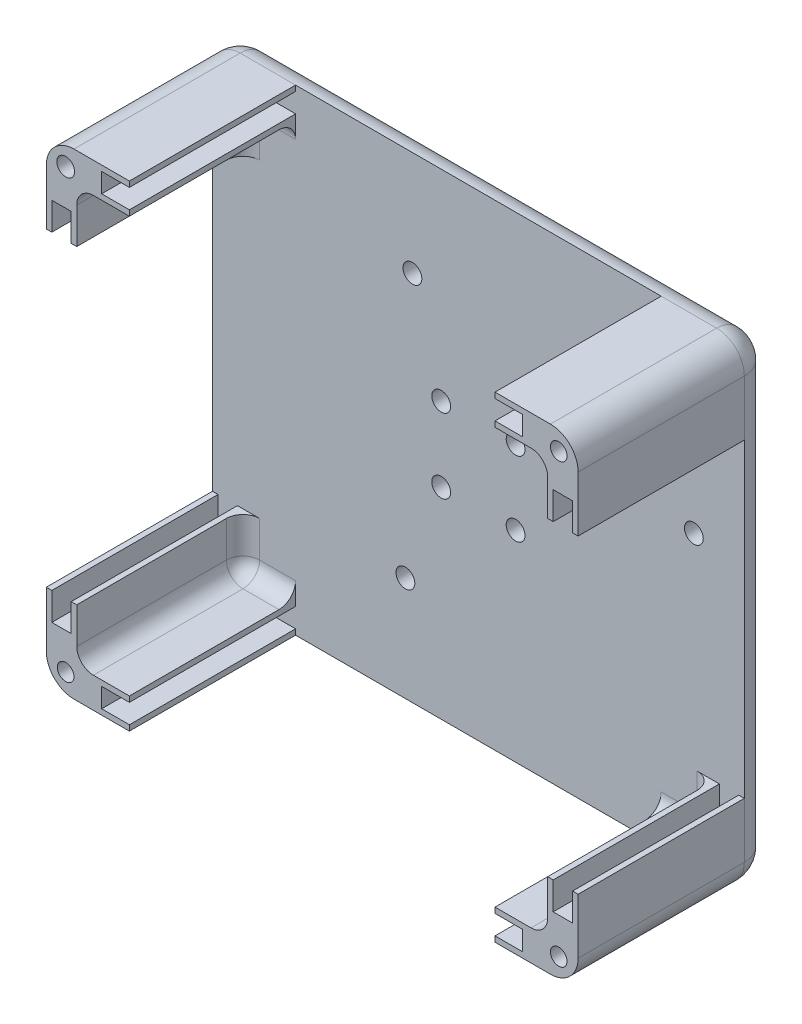
SolidWorks part; units mm, degrees
ref_plane "Plan de face" through (0, 0, 0) normal (0, 0, 1) x (1, 0, 0)
ref_plane "Plan de dessus" through (0, 0, 0) normal (0, 1, 0) x (1, 0, 0)
ref_plane "Plan de droite" through (0, 0, 0) normal (1, 0, 0) x (0, 0, -1)
sketch "Esquisse1" plane through (0, 0, 0) normal (0, 0, 1) x (1, 0, 0)
  line L1 (50.2, -56.1595) -> (-45.8, -56.1595)
  line L2 (50.2, -56.1595) -> (50.2, 29.8405)
  line L3 (50.2, 29.8405) -> (-45.8, 29.8405)
  line L4 (-45.8, -56.1595) -> (-45.8, 29.8405)
  point P0 (0, 0)
  dimension "D1" = 96
  dimension "D2" = 86
extrude "Boss.-Extru.1" add sketch "Esquisse1" along normal blind 5
sketch "trou_support_moteur" plane through (0, 0, 5) normal (0, 0, 1) x (1, 0, 0)
  circle A0 centre (2.2, -13.1595) radius 9.5 construction
  dimension "D1" = 19
sketch "Esquisse33" plane through (0, 0, 5) normal (0, 0, 1) x (1, 0, 0)
  line L1 (-4.5175, -6.4419) -> (8.9175, -6.4419) construction
  line L2 (-4.5175, -6.4419) -> (-4.5175, -19.877) construction
  line L3 (-4.5175, -19.877) -> (8.9175, -19.877) construction
  line L4 (8.9175, -6.4419) -> (8.9175, -19.877) construction
  line L5 (-4.5175, -6.4419) -> (8.9175, -19.877) construction
  line L6 (-4.5175, -19.877) -> (8.9175, -6.4419) construction
  circle A0 centre (2.2, -13.1595) radius 9.5 construction
  point P0 (2.2, -13.1595)
sketch "Esquisse2" plane through (0, 0, 5) normal (0, 0, 1) x (1, 0, 0)
  line L16 (-45.8, 29.8405) -> (-45.8, 14.8405)
  line L17 (-45.8, 29.8405) -> (-45.8, -56.1595) construction
  line L18 (-45.8, 14.8405) -> (-44.8, 14.8405)
  line L19 (-44.8, 14.8405) -> (-44.8, 19.8405)
  line L20 (-44.8, 19.8405) -> (-41.3, 19.8405)
  line L21 (-41.3, 19.8405) -> (-41.3, 14.8405)
  line L22 (-41.3, 14.8405) -> (-40.3, 14.8405)
  line L23 (-40.3, 14.8405) -> (-40.3, 24.3405)
  line L24 (-40.3, 24.3405) -> (-30.8, 24.3405)
  line L25 (-30.8, 24.3405) -> (-30.8, 25.3405)
  line L26 (-30.8, 25.3405) -> (-35.8, 25.3405)
  line L27 (-35.8, 25.3405) -> (-35.8, 28.8405)
  line L28 (-35.8, 28.8405) -> (-30.8, 28.8405)
  line L29 (-30.8, 28.8405) -> (-30.8, 29.8405)
  line L30 (50.2, 29.8405) -> (-45.8, 29.8405) construction
  line L31 (-30.8, 29.8405) -> (-45.8, 29.8405)
  dimension "D2" = 5
  dimension "D3" = 5
  dimension "D4" = 5
  dimension "D5" = 5
  dimension "D6" = 3.5
  dimension "D7" = 3.5
  dimension "D8" = 1
  dimension "D9" = 1
  dimension "D10" = 15
  dimension "D11" = 1
  dimension "D12" = 1
  dimension "D13" = 15
extrude "Boss.-Extru.4" add sketch "Esquisse2" along normal blind 30
fillet "Congé2" radius 5 4 edges at (-45.8, -13.1595, 0) (2.2, -56.1595, 0) (50.2, -13.1595, 0) (2.2, 29.8405, 0)
sketch "Esquisse4" plane through (0, 0, 35) normal (0, 0, 1) x (1, 0, 0)
  line L0 (-45.8, 29.8405) -> (-45.8, 14.8405) construction
  line L1 (-30.8, 29.8405) -> (-45.8, 29.8405) construction
  circle A0 centre (-42.3, 26.3405) radius 1.6
  dimension "D1" = 3.2
  dimension "D2" = 3.5
  dimension "D3" = 3.5
extrude "Enlèv. mat.-Extru.1" cut sketch "Esquisse4" against normal blind 10
sketch "Esquisse14" plane through (0, 0, 5) normal (0, 0, 1) x (1, 0, 0)
  line L0 (-45.8, -56.1595) -> (-45.8, -41.1595)
  line L1 (-45.8, 14.8405) -> (-45.8, -56.1595) construction
  line L2 (-45.8, -41.1595) -> (-44.8, -41.1595)
  line L3 (-44.8, -41.1595) -> (-44.8, -46.1595)
  line L4 (-44.8, -46.1595) -> (-41.3, -46.1595)
  line L5 (-41.3, -46.1595) -> (-41.3, -41.1595)
  line L6 (-41.3, -41.1595) -> (-40.3, -41.1595)
  line L7 (-40.3, -41.1595) -> (-40.3, -50.6595)
  line L8 (-40.3, -50.6595) -> (-30.8, -50.6595)
  line L9 (-30.8, -50.6595) -> (-30.8, -51.6595)
  line L10 (-30.8, -51.6595) -> (-35.8, -51.6595)
  line L11 (-35.8, -51.6595) -> (-35.8, -55.1595)
  line L12 (-35.8, -55.1595) -> (-30.8, -55.1595)
  line L13 (-30.8, -55.1595) -> (-30.8, -56.1595)
  line L14 (-45.8, -56.1595) -> (50.2, -56.1595) construction
  line L15 (-30.8, -56.1595) -> (-45.8, -56.1595)
  dimension "D1" = 15
  dimension "D2" = 15
  dimension "D3" = 5
  dimension "D4" = 5
  dimension "D5" = 3.5
  dimension "D6" = 1
  dimension "D7" = 1
  dimension "D8" = 5
  dimension "D9" = 5
  dimension "D10" = 1
  dimension "D11" = 1
  dimension "D12" = 3.5
sketch "Esquisse21" plane through (0, 0, 5) normal (0, 0, 1) x (1, 0, 0)
  line L0 (-45.8, -56.1595) -> (-45.8, -41.1595)
  line L1 (-45.8, 14.8405) -> (-45.8, -56.1595) construction
  line L2 (-45.8, -41.1595) -> (-44.8, -41.1595)
  line L3 (-44.8, -41.1595) -> (-44.8, -46.1595)
  line L4 (-44.8, -46.1595) -> (-41.3, -46.1595)
  line L5 (-41.3, -46.1595) -> (-41.3, -41.1595)
  line L6 (-41.3, -41.1595) -> (-40.3, -41.1595)
  line L7 (-40.3, -41.1595) -> (-40.3, -50.6595)
  line L8 (-40.3, -50.6595) -> (-30.8, -50.6595)
  line L9 (-30.8, -50.6595) -> (-30.8, -51.6595)
  line L10 (-30.8, -51.6595) -> (-35.8, -51.6595)
  line L11 (-35.8, -51.6595) -> (-35.8, -55.1595)
  line L12 (-35.8, -55.1595) -> (-30.8, -55.1595)
  line L13 (-30.8, -55.1595) -> (-30.8, -56.1595)
  line L14 (-45.8, -56.1595) -> (50.2, -56.1595) construction
  line L15 (-30.8, -56.1595) -> (-45.8, -56.1595)
  dimension "D1" = 15
  dimension "D2" = 15
  dimension "D3" = 5
  dimension "D4" = 5
  dimension "D5" = 5
  dimension "D6" = 5
  dimension "D7" = 1
  dimension "D8" = 1
  dimension "D9" = 3.5
  dimension "D10" = 1
  dimension "D11" = 1
  dimension "D12" = 3.5
extrude "Boss.-Extru.17" add sketch "Esquisse21" along normal blind 30
sketch "Esquisse22" plane through (0, 0, 35) normal (0, 0, 1) x (1, 0, 0)
  line L0 (-45.8, -56.1595) -> (-30.8, -56.1595) construction
  line L1 (-45.8, -41.1595) -> (-45.8, -56.1595) construction
  circle A0 centre (-42.3, -52.6595) radius 1.5
  dimension "D1" = 3
  dimension "D2" = 3.5
  dimension "D3" = 3.5
extrude "Enlèv. mat.-Extru.5" cut sketch "Esquisse22" against normal blind 10
extrude "Boss.-Extru.14" add sketch "Esquisse14" along normal blind 20
sketch "Esquisse16" plane through (0, 0, 5) normal (0, 0, 1) x (1, 0, 0)
  line L0 (50.2, 29.8405) -> (35.2, 29.8405)
  line L1 (50.2, 29.8405) -> (-30.8, 29.8405) construction
  line L2 (35.2, 29.8405) -> (35.2, 28.8405)
  line L3 (35.2, 28.8405) -> (40.2, 28.8405)
  line L4 (40.2, 28.8405) -> (40.2, 25.3405)
  line L5 (40.2, 25.3405) -> (35.2, 25.3405)
  line L6 (35.2, 25.3405) -> (35.2, 24.3405)
  line L7 (35.2, 24.3405) -> (44.7, 24.3405)
  line L8 (44.7, 24.3405) -> (44.7, 14.8405)
  line L9 (44.7, 14.8405) -> (45.7, 14.8405)
  line L10 (45.7, 14.8405) -> (45.7, 19.8405)
  line L11 (45.7, 19.8405) -> (49.2, 19.8405)
  line L12 (49.2, 19.8405) -> (49.2, 14.8405)
  line L13 (49.2, 14.8405) -> (50.2, 14.8405)
  line L14 (50.2, -56.1595) -> (50.2, 29.8405) construction
  line L15 (50.2, 14.8405) -> (50.2, 29.8405)
  dimension "D1" = 15
  dimension "D2" = 15
  dimension "D3" = 5
  dimension "D4" = 5
  dimension "D5" = 5
  dimension "D6" = 5
  dimension "D7" = 1
  dimension "D8" = 1
  dimension "D9" = 3.5
  dimension "D10" = 1
  dimension "D11" = 1
  dimension "D12" = 3.5
extrude "Boss.-Extru.15" add sketch "Esquisse16" along normal blind 30
sketch "Esquisse17" plane through (0, 0, 35) normal (0, 0, 1) x (1, 0, 0)
  line L0 (50.2, 29.8405) -> (35.2, 29.8405) construction
  line L1 (50.2, 14.8405) -> (50.2, 29.8405) construction
  circle A0 centre (46.7, 26.3405) radius 1.5
  dimension "D1" = 3
  dimension "D2" = 3.5
  dimension "D3" = 3.5
extrude "Enlèv. mat.-Extru.3" cut sketch "Esquisse17" against normal blind 10
sketch "Esquisse18" plane through (0, 0, 5) normal (0, 0, 1) x (1, 0, 0)
  line L0 (50.2, -56.1595) -> (50.2, -41.1595)
  line L1 (50.2, -56.1595) -> (50.2, 14.8405) construction
  line L2 (50.2, -41.1595) -> (49.2, -41.1595)
  line L3 (49.2, -41.1595) -> (49.2, -46.1595)
  line L4 (49.2, -46.1595) -> (45.7, -46.1595)
  line L5 (45.7, -46.1595) -> (45.7, -41.1595)
  line L6 (45.7, -41.1595) -> (44.7, -41.1595)
  line L7 (44.7, -41.1595) -> (44.7, -50.6595)
  line L8 (44.7, -50.6595) -> (35.2, -50.6595)
  line L9 (35.2, -50.6595) -> (35.2, -51.6595)
  line L10 (35.2, -51.6595) -> (40.2, -51.6595)
  line L11 (40.2, -51.6595) -> (40.2, -55.1595)
  line L12 (40.2, -55.1595) -> (35.2, -55.1595)
  line L13 (35.2, -55.1595) -> (35.2, -56.1595)
  line L14 (-30.8, -56.1595) -> (50.2, -56.1595) construction
  line L15 (35.2, -56.1595) -> (50.2, -56.1595)
  dimension "D1" = 15
  dimension "D2" = 15
  dimension "D3" = 5
  dimension "D4" = 5
  dimension "D5" = 5
  dimension "D6" = 5
  dimension "D7" = 3.5
  dimension "D8" = 1
  dimension "D9" = 1
  dimension "D10" = 1
  dimension "D11" = 1
  dimension "D12" = 3.5
extrude "Boss.-Extru.16" add sketch "Esquisse18" along normal blind 30
sketch "Esquisse19" plane through (0, 0, 35) normal (0, 0, 1) x (1, 0, 0)
  line L0 (35.2, -56.1595) -> (50.2, -56.1595) construction
  line L1 (50.2, -56.1595) -> (50.2, -41.1595) construction
  circle A0 centre (46.7, -52.6595) radius 1.5
  dimension "D1" = 3
  dimension "D2" = 3.5
  dimension "D3" = 3.5
extrude "Enlèv. mat.-Extru.4" cut sketch "Esquisse19" against normal blind 10
fillet "Congé6" radius 5 8 edges at (48.7355, 28.3761, 1.4645) (48.7355, -54.695, 1.4645) (-44.3355, -54.695, 1.4645) (-44.3355, 28.3761, 1.4645) (50.2, 29.8405, 20) (50.2, -56.1595, 20) (-45.8, -56.1595, 20) (-45.8, 29.8405, 20)
sketch "EsquisseEntretoise1" plane through (0, 0, 5) normal (0, 0, 1) x (1, 0, 0)
  line L0 (35.2, 29.8405) -> (-30.8, 29.8405) construction
  line L1 (-45.8, 14.8405) -> (-45.8, -41.1595) construction
  circle A0 centre (-9.71, 10.9605) radius 2 construction
  dimension "D1" = 4
  dimension "D2" = 18.88
  dimension "D3" = 36.09
sketch "EsquisseEntretoise2" plane through (0, 0, 5) normal (0, 0, 1) x (1, 0, 0)
  line L0 (-30.8, -56.1595) -> (35.2, -56.1595) construction
  line L2 (-45.8, 14.8405) -> (-45.8, -41.1595) construction
  circle A0 centre (-10.98, -37.2995) radius 2 construction
  dimension "D1" = 4
  dimension "D2" = 18.86
  dimension "D3" = 34.82
sketch "EsquisseEntretoise3" plane through (0, 0, 5) normal (0, 0, 1) x (1, 0, 0)
  line L0 (50.2, -41.1595) -> (50.2, 14.8405) construction
  line L1 (35.2, 29.8405) -> (-30.8, 29.8405) construction
  circle A0 centre (41.09, -4.2795) radius 2 construction
  dimension "D1" = 4
  dimension "D2" = 9.11
  dimension "D3" = 34.12
fillet "Congé14" radius 3 12 edges at (-35.55, -50.6595, 5) (-40.3, -45.9095, 5) (39.95, -50.6595, 5) (44.7, -45.9095, 5) (44.7, 19.5905, 5) (39.95, 24.3405, 5) (-40.3, 19.5905, 5) (-35.55, 24.3405, 5) (-40.3, -50.6595, 20) (44.7, -50.6595, 20) (-40.3, 24.3405, 20) (44.7, 24.3405, 20)
hole_wizard "TrouM3" positions "Esquisse34" profile "Esquisse35" hole size "M3" standard "ISO" end condition up to next
sketch "Esquisse34" plane through (0, 0, 5) normal (0, 0, 1) x (1, 0, 0)
  point P0 (-9.71, 10.9605)
  point P3 (41.09, -4.2795)
  point P6 (-10.98, -37.2995)
  point P9 (-4.5175, -19.877)
  point P12 (-4.5175, -6.4419)
  point P15 (8.9175, -6.4419)
  point P18 (8.9175, -19.877)
sketch "Esquisse35" plane through (-9.71, 10.9605, 5) normal (1, 0, 0) x (0, -1, 0)
  line L0 (0, 0) -> (0, 5)
  line L1 (0, 5) -> (1.7, 5)
  line L2 (1.7, 5) -> (1.7, 0)
  line L5 (1.7, 0) -> (0, 0)
  line L11 (0, -6.35) -> (0, 107.95) construction
  dimension "Diamètre du perçage jusqu'au prochain" = 3.4
  dimension "Profondeur du perçage jusqu'au prochain" = 5
